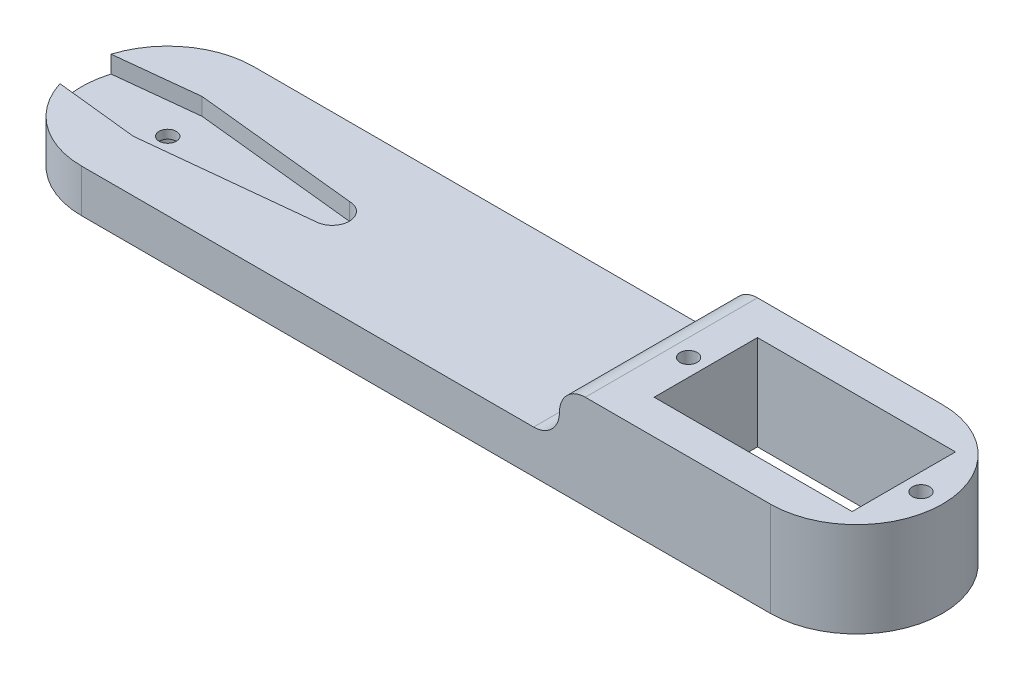
SolidWorks part; units mm, degrees
ref_plane "Front Plane" through (0, 0, 0) normal (0, 0, 1) x (1, 0, 0)
ref_plane "Top Plane" through (0, 0, 0) normal (0, 1, 0) x (1, 0, 0)
ref_plane "Right Plane" through (0, 0, 0) normal (1, 0, 0) x (0, 0, -1)
sketch "Sketch1" plane through (0, 0, 0) normal (0, 1, 0) x (1, 0, 0)
  line L1 (-40, 10) -> (40, 10)
  line L3 (-40, -10) -> (40, -10)
  arc A0 (40, -10) -> (40, 10) centre (40, 0) ccw
  arc A1 (-40, 10) -> (-40, -10) centre (-40, 0) ccw
  point P0 (0, 0)
  dimension "D1" = 20
  dimension "D2" = 80
extrude "Boss-Extrude1" add sketch "Sketch1" along normal blind 5
sketch "Sketch2" plane through (0, 5, 0) normal (0, 1, 0) x (1, 0, 0)
  line L0 (-40, 10) -> (-40, 4)
  line L1 (-58.5, 2) -> (-40, 4)
  line L2 (-40, 4) -> (-20.9058, 2)
  line L4 (-20.9058, -2) -> (-40, -4)
  line L5 (-40, -4) -> (-58.5, -2)
  line L7 (-40, -4) -> (-40, -10)
  arc A0 (-40.8549, -3.9076) -> (-39.1711, -3.9132) centre (-40, 0) ccw
  arc A1 (-20.9058, -2) -> (-20.9058, 2) centre (-20.9058, 0) ccw
  arc A2 (-58.5, 2) -> (-58.5, -2) centre (-58.5, 0) ccw
  arc A3 (-39.1711, 3.9132) -> (-40.8549, 3.9076) centre (-40, 0) ccw
  point P6 (-21.5, 0)
  point P7 (-58.5, 0)
  arc M3 (-40, 10) -> (-40, -10) centre (-40, 0) ccw
  dimension "D1" = 8
  dimension "D4" = 4
  dimension "D5" = 4
  dimension "D2" = 18.5
  dimension "D3" = 18.5
extrude "Cut-Extrude1" cut sketch "Sketch2" against normal blind 2 contours L4 A1 L2 L1 L5 M3 region at (-35.8869, 5, 0)
sketch "Sketch3" plane through (0, 5, 0) normal (0, 1, 0) x (1, 0, 0)
  line L0 (-40, 10) -> (-40, -10)
  circle A0 centre (-40, 0) radius 1
  dimension "D1" = 2
extrude "Cut-Extrude2" cut sketch "Sketch3" against normal through all contours L0 A0 | L0 A0 region at (-39.5756, 5, 0) region at (-40.4244, 5, 0)
sketch "Sketch4" plane through (0, 0, 0) normal (0, -1, 0) x (1, 0, 0)
  circle A0 centre (-40, 0) radius 3
  dimension "D1" = 6
extrude "Cut-Extrude3" cut sketch "Sketch4" against normal blind 2
sketch "Sketch5" plane through (0, 5, 0) normal (0, 1, 0) x (1, 0, 0)
  line L0 (40, 10) -> (40, -10)
  line L2 (22.5, 6) -> (45.5, 6)
  line L3 (22.5, 6) -> (22.5, -6)
  line L4 (22.5, -6) -> (45.5, -6)
  line L5 (45.5, 6) -> (45.5, -6)
  arc A0 (40, -10) -> (40, 10) centre (40, 0) ccw construction
  circle A1 centre (20.5, 0) radius 1
  circle A2 centre (47.5, 0) radius 1
  point P7 (45.5, 0)
  point P8 (40, 0)
  point P9 (45.5, 0)
  point P10 (45.5, 6)
  point P11 (45.5, -6)
  point P12 (22.5, 6)
  point P17 (47.5, 0)
  point P18 (20.5, 0)
  dimension "D7" = 2
  dimension "D8" = 2
  dimension "D1" = 5.5
  dimension "D2" = 6
  dimension "D3" = 6
  dimension "D4" = 23
  dimension "D5" = 2
  dimension "D6" = 2
extrude "Cut-Extrude4" cut sketch "Sketch5" against normal through all contours L3 L4 L0 L2 | L5 L2 L0 L4 | A2 | A1 region at (42.75, 5, 0) region at (31.25, 5, 0)
sketch "Sketch6" plane through (0, 5, 0) normal (0, 1, 0) x (1, 0, 0)
  line L0 (15.5013, 10) -> (15.5013, -10)
  line L1 (40, 10) -> (-40, 10) construction
  line L2 (-40, -10) -> (40, -10) construction
  line L3 (15.5013, -10) -> (40, -10)
  line L5 (40, 10) -> (15.5013, 10)
  line L7 (22.5, 6) -> (45.5, 6)
  line L8 (22.5, 6) -> (22.5, -6)
  line L9 (22.5, -6) -> (45.5, -6)
  line L10 (45.5, 6) -> (45.5, -6)
  arc A0 (40, -10) -> (40, 10) centre (40, 0) ccw
  circle A1 centre (20.5, 0) radius 1
  circle A2 centre (47.5, 0) radius 1
extrude "Boss-Extrude2" add sketch "Sketch6" along normal blind 6 contours A0 L5 L0 L3 | A1 | A2 | L8 L7 L10 L9
fillet "Fillet1" radius 3 1 edges at (15.5013, 11, 0) type face fillet first side face at (20.5, 11, 1) second side face at (15.5013, 8, 0)
fillet "Fillet2" radius 3 1 edges at (15.5013, 5, 0) type face fillet first side face at (15.5013, 6.5, 0) second side face at (-27.0218, 5, 0)
sketch "Sketch7" plane through (0, 0, 0) normal (0, -1, 0) x (1, 0, 0)
  circle A0 centre (20.5, 0) radius 1.5
  circle A1 centre (47.5, 0) radius 1.5
  dimension "D1" = 3
  dimension "D2" = 3
extrude "Cut-Extrude5" cut sketch "Sketch7" against normal blind 4
sketch "Sketch8" plane through (0, 0, -10) normal (0, 0, -1) x (-1, 0, 0)
  line L0 (-40, 0) -> (40, 0) construction
  circle A0 centre (0, 2.5) radius 1.75
  point P0 (0, 0)
  point P1 (0, 2.5)
  dimension "D2" = 3.5
  dimension "D1" = 2.5
extrude "Cut-Extrude6" cut sketch "Sketch8" against normal blind 10
